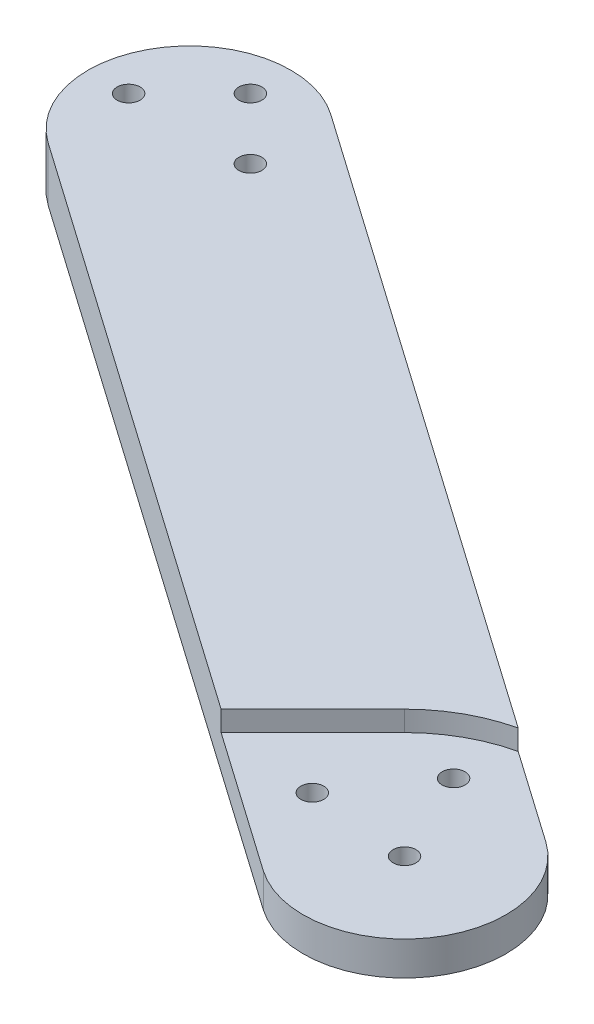
SolidWorks part; units mm, degrees
ref_plane "Front Plane" through (0, 0, 0) normal (0, 0, 1) x (1, 0, 0)
ref_plane "Top Plane" through (0, 0, 0) normal (0, 1, 0) x (1, 0, 0)
ref_plane "Right Plane" through (0, 0, 0) normal (1, 0, 0) x (0, 0, -1)
sketch "Sketch1" plane through (0, 0, 0) normal (0, 1, 0) x (1, 0, 0)
  line L0 (0, 0) -> (106.066, 106.066) construction
  line L1 (3.4641, 17.5) -> (1.7321, 20.5)
  line L2 (1.7321, 20.5) -> (-1.7321, 20.5)
  line L3 (-1.7321, 20.5) -> (-3.4641, 17.5)
  line L4 (-3.4641, 17.5) -> (-1.7321, 14.5)
  line L5 (-1.7321, 14.5) -> (1.7321, 14.5)
  line L6 (1.7321, 14.5) -> (3.4641, 17.5)
  line L7 (-17.5, -3.4641) -> (-14.5, -1.7321)
  line L8 (-14.5, -1.7321) -> (-14.5, 1.7321)
  line L9 (-14.5, 1.7321) -> (-17.5, 3.4641)
  line L10 (-17.5, 3.4641) -> (-20.5, 1.7321)
  line L11 (-20.5, 1.7321) -> (-20.5, -1.7321)
  line L12 (-20.5, -1.7321) -> (-17.5, -3.4641)
  line L13 (-3.4641, -17.5) -> (-1.7321, -20.5)
  line L14 (-1.7321, -20.5) -> (1.7321, -20.5)
  line L15 (1.7321, -20.5) -> (3.4641, -17.5)
  line L16 (3.4641, -17.5) -> (1.7321, -14.5)
  line L17 (1.7321, -14.5) -> (-1.7321, -14.5)
  line L18 (-1.7321, -14.5) -> (-3.4641, -17.5)
  line L19 (17.5, 3.4641) -> (14.5, 1.7321)
  line L20 (14.5, 1.7321) -> (14.5, -1.7321)
  line L21 (14.5, -1.7321) -> (17.5, -3.4641)
  line L22 (17.5, -3.4641) -> (20.5, -1.7321)
  line L23 (20.5, -1.7321) -> (20.5, 1.7321)
  line L24 (20.5, 1.7321) -> (17.5, 3.4641)
  line L25 (-15.5563, 15.5563) -> (90.5097, 121.6224)
  line L26 (15.5563, -15.5563) -> (121.6224, 90.5097)
  line L27 (106.066, 106.066) -> (0, 180.3342) construction
  line L28 (97.4624, 93.7787) -> (-8.6036, 168.047)
  line L29 (114.6697, 118.3533) -> (8.6036, 192.6215)
  line L30 (99.7189, 119.6662) -> (91.1152, 107.3789) construction
  line L31 (106.9626, 109.4121) -> (103.6165, 108.5155)
  line L32 (103.6165, 108.5155) -> (102.72, 105.1694)
  line L33 (102.72, 105.1694) -> (105.1694, 102.72)
  line L34 (105.1694, 102.72) -> (108.5155, 103.6165)
  line L35 (108.5155, 103.6165) -> (109.4121, 106.9626)
  line L36 (109.4121, 106.9626) -> (106.9626, 109.4121)
  line L37 (-9, 180.3342) -> (9, 180.3342) construction
  line L38 (90.2186, 104.0328) -> (93.5647, 104.9294)
  line L39 (93.5647, 104.9294) -> (94.4613, 108.2754)
  line L40 (94.4613, 108.2754) -> (92.0118, 110.7249)
  line L41 (92.0118, 110.7249) -> (88.6657, 109.8284)
  line L42 (88.6657, 109.8284) -> (87.7692, 106.4823)
  line L43 (87.7692, 106.4823) -> (90.2186, 104.0328)
  line L44 (100.6154, 123.0122) -> (97.2694, 122.1156)
  line L45 (97.2694, 122.1156) -> (96.3728, 118.7696)
  line L46 (96.3728, 118.7696) -> (98.8223, 116.3201)
  line L47 (98.8223, 116.3201) -> (102.1684, 117.2167)
  line L48 (102.1684, 117.2167) -> (103.0649, 120.5627)
  line L49 (103.0649, 120.5627) -> (100.6154, 123.0122)
  line L50 (-3.4641, 17.5) -> (3.4641, 17.5)
  line L51 (-3.4641, 17.5) -> (-3.4641, 23.8539)
  line L52 (-3.4641, 23.8539) -> (3.4641, 23.8539)
  line L53 (3.4641, 17.5) -> (3.4641, 23.8539)
  line L54 (-17.5, -3.4641) -> (-25.5814, -3.4641)
  line L55 (-17.5, -3.4641) -> (-17.5, 3.4641)
  line L56 (-17.5, 3.4641) -> (-25.5814, 3.4641)
  line L57 (-25.5814, -3.4641) -> (-25.5814, 3.4641)
  line L58 (-3.4641, -17.5) -> (3.4641, -17.5)
  line L59 (-3.4641, -17.5) -> (-3.4641, -25.8241)
  line L60 (-3.4641, -25.8241) -> (3.4641, -25.8241)
  line L61 (3.4641, -17.5) -> (3.4641, -25.8241)
  line L62 (17.5, 3.4641) -> (24.0978, 3.4641)
  line L63 (17.5, 3.4641) -> (17.5, -3.4641)
  line L64 (17.5, -3.4641) -> (24.0978, -3.4641)
  line L65 (24.0978, 3.4641) -> (24.0978, -3.4641)
  line L66 (-111.8183, 250.0982) -> (111.8183, 250.0982)
  line L67 (-111.8183, 250.0982) -> (-111.8183, 175.3342)
  line L68 (-111.8183, 175.3342) -> (111.8183, 175.3342)
  line L69 (111.8183, 250.0982) -> (111.8183, 175.3342)
  line L70 (-15.8392, 15.8392) -> (90.2268, 121.9052)
  line L71 (15.8392, -15.8392) -> (121.9052, 90.2268)
  circle A0 centre (0, 0) radius 14
  circle A1 centre (0, 0) radius 21
  circle A2 centre (0, 0) radius 17.5 construction
  circle A3 centre (0, 17.5) radius 1.7
  circle A4 centre (17.5, 0) radius 1.7
  circle A5 centre (0, -17.5) radius 1.7
  circle A6 centre (-17.5, 0) radius 1.7
  circle A7 centre (0, 17.5) radius 3 construction
  circle A8 centre (-17.5, 0) radius 3 construction
  circle A9 centre (0, -17.5) radius 3 construction
  circle A10 centre (17.5, 0) radius 3 construction
  arc A12 (-15.5563, 15.5563) -> (15.5563, -15.5563) centre (0, 0) ccw
  arc A13 (121.6224, 90.5097) -> (90.5097, 121.6224) centre (106.066, 106.066) ccw
  arc A14 (97.4624, 93.7787) -> (114.6697, 118.3533) centre (106.066, 106.066) ccw
  arc A15 (8.6036, 192.6215) -> (-8.6036, 168.047) centre (0, 180.3342) ccw
  circle A16 centre (106.066, 106.066) radius 1.7
  circle A17 centre (106.066, 106.066) radius 3 construction
  circle A18 centre (99.7189, 119.6662) radius 1.7
  circle A19 centre (91.1152, 107.3789) radius 1.7
  circle A20 centre (91.1152, 107.3789) radius 3 construction
  circle A21 centre (99.7189, 119.6662) radius 3 construction
  circle A22 centre (0, 189.3342) radius 1.7
  circle A23 centre (9, 180.3342) radius 1.7
  circle A24 centre (-9, 180.3342) radius 1.7
  arc A25 (121.9052, 90.2268) -> (90.2268, 121.9052) centre (106.066, 106.066) ccw
  arc A26 (-15.8392, 15.8392) -> (15.8392, -15.8392) centre (0, 0) ccw
  point P14 (53.033, 53.033)
  point P50 (53.033, 143.2001)
  point P66 (95.417, 113.5225)
  point P102 (0, 180.3342)
  dimension "D1" = 28
  dimension "D2" = 42
  dimension "D4" = 3.4
  dimension "D5" = 3.4
  dimension "D6" = 3.4
  dimension "D7" = 3.4
  dimension "D8" = 6
  dimension "D3" = 3.5
  dimension "D9" = 3.5
  dimension "D10" = 6
  dimension "D11" = 6
  dimension "D12" = 6
  dimension "D13" = 22
  dimension "D17" = 15
  dimension "D18" = 3.4
  dimension "D19" = 6
  dimension "D20" = 3.4
  dimension "D22" = 3.4
  dimension "D23" = 6
  dimension "D24" = 6
  dimension "D29" = 3.4
  dimension "D30" = 3.4
  dimension "D31" = 3.4
  dimension "D14" = 45
  dimension "D15" = 150
  dimension "D16" = 80
  dimension "D21" = 15
  dimension "D25" = 13
  dimension "D26" = 5
  dimension "D27" = 9
  dimension "D28" = 9
  dimension "D32" = 0.4
extrude "Boss-Extrude1" add sketch "Sketch1" along normal blind 8 contours L28 A15 L29 A14
extrude "Cut-Extrude1" cut sketch "Sketch1<11>" against normal blind 3 from surface contours A25 L70 A26 L71 starting at face at (53.033, 8, -143.2001)
sketch "Sketch1<11>" plane through (0, 0, 0) normal (0, 1, 0) x (1, 0, 0) same geometry as "Sketch1"
extrude "Cut-Extrude2" cut sketch "Sketch1<12>" along normal blind 4 contours L29 A15 L68 A24 A23 A22 region at (4.3544, 0, -183.2924)
sketch "Sketch1<12>" plane through (0, 0, 0) normal (0, 1, 0) x (1, 0, 0) same geometry as "Sketch1"
extrude "Cut-Extrude3" cut sketch "Sketch1<13>" along normal through all both and the other way through all contours A22 | A24 | A23 | A18 | A19 | A16 region at (106.066, 0, -106.066) region at (99.7189, 0, -119.6662) region at (91.1152, 0, -107.3789) region at (0, 0, -189.3342) region at (9, 0, -180.3342) region at (-9, 0, -180.3342)
sketch "Sketch1<13>" plane through (0, 0, 0) normal (0, 1, 0) x (1, 0, 0) same geometry as "Sketch1"
